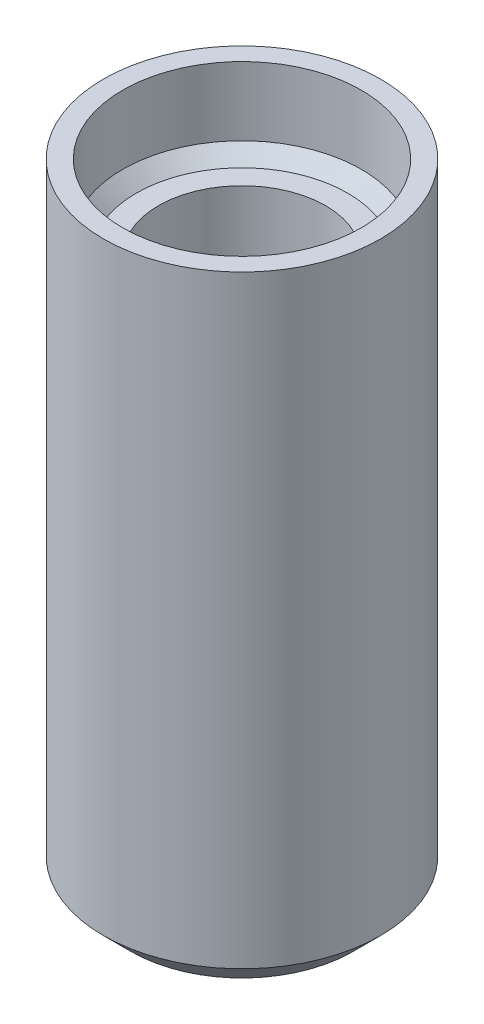
SolidWorks part; units mm, degrees
ref_plane "Front Plane" through (0, 0, 0) normal (0, 0, 1) x (1, 0, 0)
ref_plane "Top Plane" through (0, 0, 0) normal (0, 1, 0) x (1, 0, 0)
ref_plane "Right Plane" through (0, 0, 0) normal (1, 0, 0) x (0, 0, -1)
sketch "Sketch1" plane through (0, 0, 0) normal (0, 1, 0) x (1, 0, 0)
  line L0 (-2.5652, -1.65) -> (2.5652, -1.65)
  circle A0 centre (0, 0) radius 3.05
  circle A1 centre (0, 0) radius 5.05
  dimension "D1" = 6.1
  dimension "D3" = 1.65
  dimension "D2" = 2
extrude "Boss-Extrude1" add sketch "Sketch1" along normal blind 20 contours A1 A0 | L0 A0 region at (0, 0, 2.2227) region at (-4.9072, 0, 0)
sketch "Sketch2" plane through (0, 0, 0) normal (0, -1, 0) x (1, 0, 0)
  circle A1 centre (0, 0) radius 5.05
  circle A2 centre (0, 0) radius 5.05
  dimension "D1" = 0
extrude "Boss-Extrude2" add sketch "Sketch2" against normal blind 2
sketch "Sketch4" plane through (0, 20, 0) normal (0, 1, 0) x (1, 0, 0)
  circle A0 centre (0, 0) radius 4.35
  circle A1 centre (0, 0) radius 5.05
  circle A2 centre (0, 0) radius 5.05
  dimension "D1" = 0
  dimension "D2" = 0.7
extrude "Boss-Extrude3" add sketch "Sketch4" along normal blind 3
chamfer "Chamfer1" distance 1 angle 45 1 edges at (0, 0, 5.05)
chamfer "Chamfer2" distance 0.5 angle 45 1 edges at (0, 20, 4.35)
sketch "Sketch5" plane through (0, 0, 0) normal (0, -1, 0) x (1, 0, 0)
  line L0 (-1.326, 0) -> (1.326, 0) construction
  line L1 (-3.5217, -2) -> (3.5217, -2) construction
  circle A0 centre (0, 0) radius 4.05 construction
  text T0 "<b>9</b>" font "Calibri" height in points 16
  dimension "D1" = 2
extrude "Cut-Extrude1" cut sketch "Sketch5" against normal blind 0.4
extrude "Boss-Extrude4" add sketch "Sketch5<2>" against normal blind 0.4 separate body
sketch "Sketch5<2>" plane through (0, 0, 0) normal (0, -1, 0) x (1, 0, 0) same geometry as "Sketch5"
equation "\"ID\"= 6.3"
equation "\"notch\"= 6.3 / 2 - 1.5"
equation "\"D3@Sketch1\"=\"notch\""
